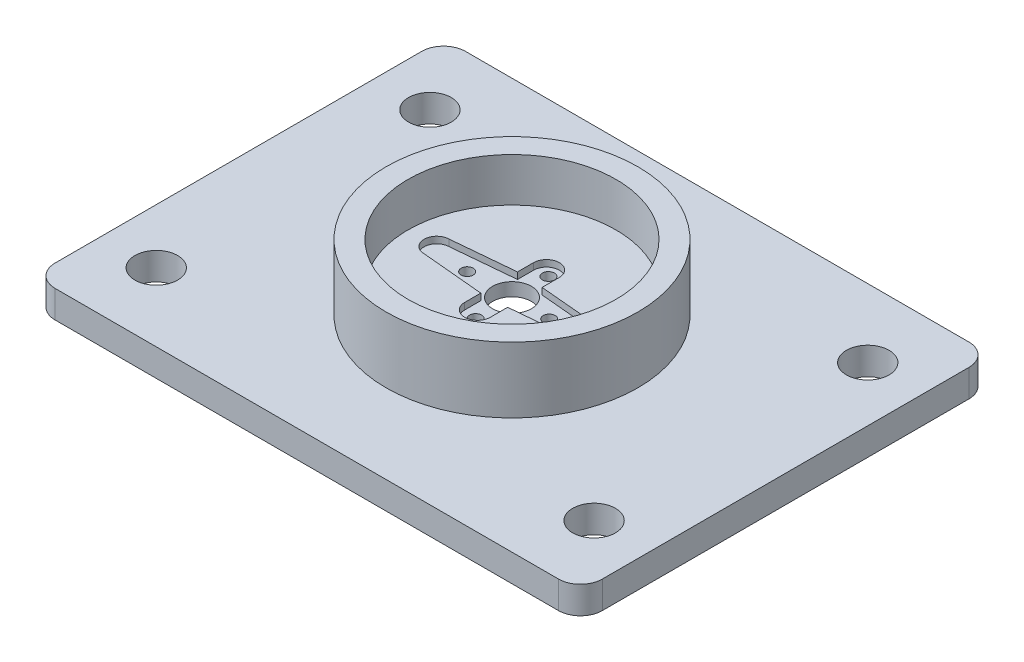
SolidWorks part; units mm, degrees
ref_plane "Plan de face" through (0, 0, 0) normal (0, 0, 1) x (1, 0, 0)
ref_plane "Plan de dessus" through (0, 0, 0) normal (0, 1, 0) x (1, 0, 0)
ref_plane "Plan de droite" through (0, 0, 0) normal (1, 0, 0) x (0, 0, -1)
sketch "Esquisse1" plane through (0, 0, 0) normal (0, 1, 0) x (1, 0, 0)
  line L0 (0, 0) -> (50, 0) construction
  line L1 (-50, 37.5) -> (50, 37.5)
  line L2 (-50, 37.5) -> (-50, -37.5)
  line L3 (-50, -37.5) -> (50, -37.5)
  line L4 (50, 37.5) -> (50, -37.5)
  line L5 (0, 0) -> (0, -37.5) construction
  circle A0 centre (-40, 25) radius 3.9
  circle A1 centre (-40, -25) radius 3.9
  circle A2 centre (40, -25) radius 3.9
  circle A3 centre (40, 25) radius 3.9
  arc A4 (-46, 37.5) -> (-50, 33.5) centre (-46, 33.5) ccw
  arc A5 (46, 37.5) -> (50, 33.5) centre (46, 33.5) cw
  arc A6 (-46, -37.5) -> (-50, -33.5) centre (-46, -33.5) cw
  arc A7 (46, -37.5) -> (50, -33.5) centre (46, -33.5) ccw
  point P4 (0, 37.5)
  point P6 (50, 0)
  point P20 (-50, 33.5)
  dimension "D3" = 7.8
  dimension "D6" = 4
  dimension "D1" = 100
  dimension "D2" = 75
  dimension "D4" = 10
  dimension "D5" = 12.5
extrude "Boss.-Extru.1" add sketch "Esquisse1" along normal blind 5 contours L3 A7 L4 A5 L1 A4 L2 A6 A1 A0 A2 A3 region at (0, 0, 0)
sketch "Esquisse2" plane through (0, 5, 0) normal (0, 1, 0) x (1, 0, 0)
  circle A0 centre (0, 0) radius 23
  circle A1 centre (0, 0) radius 19
  dimension "D1" = 38
  dimension "D2" = 4
extrude "Boss.-Extru.2" add sketch "Esquisse2" along normal blind 12
sketch "Esquisse5" plane through (0, 5, 0) normal (0, 1, 0) x (1, 0, 0)
  circle A1 centre (0, 0) radius 19
  circle A2 centre (0, 0) radius 19
  dimension "D1" = 0
extrude "Boss.-Extru.3" add sketch "Esquisse5" along normal blind 4
sketch "Esquisse8" plane through (0, 9, 0) normal (0, 1, 0) x (1, 0, 0)
  line L0 (0.1387, 3.3471) -> (16.25, 1.9)
  line L1 (0.1387, -3.3471) -> (16.25, -1.9)
  line L2 (-3.35, 0) -> (18.15, 0) construction
  line L3 (0, 0) -> (0, -3.35) construction
  line L4 (-1.85, -6.3) -> (1.85, -6.3)
  line L5 (-1.85, 0) -> (1.85, 0)
  line L6 (-1.85, -6.3) -> (-1.85, 6.3)
  line L7 (-1.85, 6.3) -> (1.85, 6.3)
  line L8 (1.85, -6.3) -> (1.85, 6.3)
  line L9 (-1.85, 2.9) -> (-1.85, -2.9) construction
  line L10 (-1.85, 2.9) -> (-13.75, 1.8)
  line L11 (-13.75, -1.8) -> (-1.85, -2.9)
  line L12 (-1.896, 3.3979) -> (-13.7745, 2.2999)
  line L13 (-13.7745, -2.2999) -> (-1.896, -3.3979)
  line L14 (-1.35, -6.3) -> (-1.35, 6.3)
  line L15 (2.35, -6.3) -> (2.35, 6.3)
  line L16 (0.094, 2.8491) -> (16.2293, 1.3998)
  line L17 (0.094, -2.8491) -> (16.2293, -1.3998)
  line L18 (-2.35, 6.3) -> (-2.35, 3.3559)
  line L19 (2.35, 6.3) -> (2.35, -6.3)
  line L20 (-2.35, -6.3) -> (-2.35, -3.3559)
  circle A0 centre (0, 0) radius 19 construction
  circle A1 centre (0, 0) radius 19
  arc A2 (0.1387, 3.3471) -> (-0.1387, 3.3471) centre (0, 0) ccw
  arc A3 (16.25, -1.9) -> (16.25, 1.9) centre (16.25, 0) ccw
  circle A4 centre (0, 0) radius 1.1
  arc A5 (-0.1387, 3.3471) -> (0.1387, 3.3471) centre (0, 0) cw
  arc A6 (-0.1387, -3.3471) -> (0.1387, -3.3471) centre (0, 0) ccw
  arc A7 (0.1387, -3.3471) -> (-0.1387, -3.3471) centre (0, 0) cw
  arc A8 (1.85, 6.3) -> (-1.85, 6.3) centre (0, 6.3) ccw
  arc A9 (1.85, -6.3) -> (-1.85, -6.3) centre (0, -6.3) cw
  arc A10 (-13.75, 1.8) -> (-13.75, -1.8) centre (-13.75, 0) ccw
  arc A11 (-13.7745, 2.2999) -> (-13.7745, -2.2999) centre (-13.75, 0) ccw
  arc A12 (1.35, -6.3) -> (-1.35, -6.3) centre (0, -6.3) cw
  arc A13 (2.35, 6.3) -> (-2.35, 6.3) centre (0, 6.3) ccw
  arc A14 (16.2293, -1.3998) -> (16.2293, 1.3998) centre (16.25, 0) ccw
  arc A15 (2.35, -6.3) -> (-2.35, -6.3) centre (0, -6.3) cw
  point P5 (0, 3.35)
  point P6 (16.25, 1.9)
  point P11 (-3.35, 0)
  point P12 (18.15, 0)
  point P20 (-15.55, 0)
  point P29 (0, 0)
  point P36 (0, 8.15)
  point P37 (0, -8.15)
  point P38 (-1.85, 0)
  dimension "D1" = 6.7
  dimension "D2" = 3.8
  dimension "D3" = 2.2
  dimension "D6" = 3.6
  dimension "D4" = 3.7
  dimension "D5" = 16.3
  dimension "D7" = 33.7
  dimension "D8" = 21.5
  dimension "D9" = 5.8
  dimension "D10" = 5.133
  dimension "D11" = 0.5
extrude "Enlèv. mat.-Extru.4" cut sketch "Esquisse8" against normal blind 1.2 contours L10 A10 L11 L6 | A15 L15 L1 L8 A9 L6 L11 A10 L10 A8 L0 A13 L18 L12 A11 L13 L20 | L7 A8 | L5 L14 L7 L6 | A4 L5 L8 L7 L14 | L5 A4 | L5 A4 | A4 L5 L14 L4 L8 | L4 L14 L5 L6 | A12 L4 | L4 A12 A9 | L8 L17 L15 L16 | L17 L8 L1 L15 | A14 L17 L15 L1 A3 L0 L16 | L17 A14 L16 L15 | L8 L16 L15 L0 region at (2.1026, 9, -4.7467) region at (2.1, 9, -2.92) region at (0.276, 9, -3.4293) region at (9.2848, 9, -2.3549) region at (2.0993, 9, 0) region at (0, 9, -7.0852) region at (9.0137, 9, 0) region at (0.276, 9, 3.4293) region at (-1.6, 9, -3.15) region at (2.1, 9, 2.92) region at (0, 9, 0.4669) region at (0, 9, -0.4669) region at (-1.6, 9, 3.15) region at (-7.9345, 9, 0) region at (0, 9, 7.6914) region at (0, 9, 6.873)
sketch "Esquisse9" plane through (0, 7.8, 0) normal (0, 1, 0) x (1, 0, 0)
  line L8 (2.35, -6.3) -> (2.35, -3.1485)
  line L9 (2.35, -3.1485) -> (16.25, -1.9)
  line L10 (16.25, 1.9) -> (2.35, 3.1485)
  line L11 (2.35, 3.1485) -> (2.35, 6.3)
  line L12 (-2.35, 6.3) -> (-2.35, 3.3559)
  line L13 (-2.35, 3.3559) -> (-13.7745, 2.2999)
  line L14 (-13.7745, -2.2999) -> (-2.35, -3.3559)
  line L15 (-2.35, -3.3559) -> (-2.35, -6.3)
  line L16 (2.35, -6.3) -> (2.35, -3.1485)
  line L17 (2.35, -3.1485) -> (16.25, -1.9)
  line L18 (16.25, 1.9) -> (2.35, 3.1485)
  line L19 (2.35, 3.1485) -> (2.35, 6.3)
  line L20 (-2.35, 6.3) -> (-2.35, 3.3559)
  line L21 (-2.35, 3.3559) -> (-13.7745, 2.2999)
  line L22 (-13.7745, -2.2999) -> (-2.35, -3.3559)
  line L23 (-2.35, -3.3559) -> (-2.35, -6.3)
  circle A0 centre (0, 0) radius 3.55
  arc A4 (16.25, -1.9) -> (16.25, 1.9) centre (16.25, 0) ccw
  arc A5 (2.35, 6.3) -> (-2.35, 6.3) centre (0, 6.3) ccw
  arc A6 (-13.7745, 2.2999) -> (-13.7745, -2.2999) centre (-13.75, 0) ccw
  arc A7 (-2.35, -6.3) -> (2.35, -6.3) centre (0, -6.3) ccw
  arc A8 (16.25, -1.9) -> (16.25, 1.9) centre (16.25, 0) ccw
  arc A9 (2.35, 6.3) -> (-2.35, 6.3) centre (0, 6.3) ccw
  arc A10 (-13.7745, 2.2999) -> (-13.7745, -2.2999) centre (-13.75, 0) ccw
  arc A11 (-2.35, -6.3) -> (2.35, -6.3) centre (0, -6.3) ccw
  dimension "D2" = 7.1
  dimension "D1" = 0
extrude "Enlèv. mat.-Extru.5" cut sketch "Esquisse9" against normal through all contours A0
sketch "Esquisse6" plane through (0, 0, 0) normal (0, -1, 0) x (1, 0, 0)
  circle A1 centre (0, 0) radius 19
  circle A2 centre (0, 0) radius 19
  dimension "D1" = 0
extrude "Enlèv. mat.-Extru.3" cut sketch "Esquisse6" against normal offset from surface (5.4 mm away) 2.4 up to face at (0, 7.8, 3.55)
sketch "Esquisse10" plane through (0, 7.8, 0) normal (0, 1, 0) x (1, 0, 0)
  line L1 (0, 0) -> (0, -3.35) construction
  line L2 (16.55, 0) -> (18.15, 0) construction
  line L3 (-13.95, 0) -> (-12.03, 0) construction
  line L4 (-12.03, 0) -> (-10.11, 0) construction
  line L5 (-10.11, 0) -> (-8.19, 0) construction
  line L6 (-8.19, 0) -> (-6.27, 0) construction
  line L7 (-6.27, 0) -> (-4.35, 0) construction
  line L8 (2.35, -6.3) -> (2.35, -3.1485)
  line L9 (2.35, -3.1485) -> (16.25, -1.9)
  line L10 (16.25, 1.9) -> (2.35, 3.1485)
  line L11 (2.35, 3.1485) -> (2.35, 6.3)
  line L12 (-2.35, 6.3) -> (-2.35, 3.3559)
  line L13 (-2.35, 3.3559) -> (-13.7745, 2.2999)
  line L14 (-13.7745, -2.2999) -> (-2.35, -3.3559)
  line L15 (-2.35, -3.3559) -> (-2.35, -6.3)
  line L16 (2.35, -6.3) -> (2.35, -3.1485)
  line L17 (2.35, -3.1485) -> (16.25, -1.9)
  line L18 (16.25, 1.9) -> (2.35, 3.1485)
  line L19 (2.35, 3.1485) -> (2.35, 6.3)
  line L20 (-2.35, 6.3) -> (-2.35, 3.3559)
  line L21 (-2.35, 3.3559) -> (-13.7745, 2.2999)
  line L22 (-13.7745, -2.2999) -> (-2.35, -3.3559)
  line L23 (-2.35, -3.3559) -> (-2.35, -6.3)
  line L24 (4.85, 0) -> (6.8, 0) construction
  line L25 (6.8, 0) -> (8.75, 0) construction
  line L26 (8.75, 0) -> (10.7, 0) construction
  line L27 (10.7, 0) -> (12.65, 0) construction
  line L28 (12.65, 0) -> (14.6, 0) construction
  line L29 (14.6, 0) -> (16.55, 0) construction
  line L30 (0, 6.65) -> (0, 4.35) construction
  line L31 (0, -4.35) -> (0, -6.65) construction
  circle A0 centre (0, 4.35) radius 0.5
  circle A1 centre (0, 6.65) radius 0.5
  circle A2 centre (4.85, 0) radius 0.5
  circle A3 centre (0, 0) radius 3.35
  arc A4 (16.25, -1.9) -> (16.25, 1.9) centre (16.25, 0) ccw
  arc A5 (2.35, 6.3) -> (-2.35, 6.3) centre (0, 6.3) ccw
  arc A6 (-13.7745, 2.2999) -> (-13.7745, -2.2999) centre (-13.75, 0) ccw
  arc A7 (-2.35, -6.3) -> (2.35, -6.3) centre (0, -6.3) ccw
  arc A8 (16.25, -1.9) -> (16.25, 1.9) centre (16.25, 0) ccw
  arc A9 (2.35, 6.3) -> (-2.35, 6.3) centre (0, 6.3) ccw
  arc A10 (-13.7745, 2.2999) -> (-13.7745, -2.2999) centre (-13.75, 0) ccw
  arc A11 (-2.35, -6.3) -> (2.35, -6.3) centre (0, -6.3) ccw
  circle A12 centre (6.8, 0) radius 0.5
  circle A13 centre (8.75, 0) radius 0.5
  circle A14 centre (10.7, 0) radius 0.5
  circle A15 centre (12.65, 0) radius 0.5
  circle A16 centre (14.6, 0) radius 0.5
  circle A17 centre (16.55, 0) radius 0.5
  circle A18 centre (0, -6.65) radius 0.5
  circle A19 centre (0, -4.35) radius 0.5
  circle A20 centre (-4.35, 0) radius 0.5
  circle A21 centre (-6.27, 0) radius 0.5
  circle A22 centre (-8.19, 0) radius 0.5
  circle A23 centre (-10.11, 0) radius 0.5
  circle A24 centre (-12.03, 0) radius 0.5
  circle A25 centre (-13.95, 0) radius 0.5
  circle A26 centre (6.8, 0) radius 1.1
  circle A27 centre (12.65, 0) radius 1.1
  circle A28 centre (-8.19, 0) radius 1.1
  circle A29 centre (0, 6.65) radius 1.1
  circle A30 centre (0, -6.65) radius 1.1
  point P12 (16.55, 0)
  point P19 (3.35, 0)
  point P21 (0, 3.35)
  point P49 (-3.35, 0)
  point P50 (-15.5498, -0.0279)
  point P51 (0, 8.15)
  point P60 (0, -7.2778)
  dimension "D3" = 1
  dimension "D9" = 6.7
  dimension "D10" = 1.92
  dimension "D14" = 2.2
  dimension "D2" = 1.6
  dimension "D4" = 1
  dimension "D5" = 1.5
  dimension "D6" = 1.5
  dimension "D7" = 1
  dimension "D8" = 1.6
  dimension "D11" = 2.3
  dimension "D12" = 1.95
  dimension "D13" = 1
  dimension "D1" = 0
extrude "Enlèv. mat.-Extru.6" cut sketch "Esquisse10" against normal through all contours A29 A1 | A1 | A18 | A30 A18 | A28 A22 | A22 | A26 A12 | A12 | A27 A15 | A15 region at (0, 7.8, -6.65) region at (6.8, 7.8, 0) region at (12.65, 7.8, 0) region at (0, 7.8, 6.65) region at (-8.19, 7.8, 0) region at (5.7311, 7.8, 0) region at (11.5811, 7.8, 0) region at (-9.2589, 7.8, 0) region at (-1.0689, 7.8, -6.65) region at (-1.0689, 7.8, 6.65)
